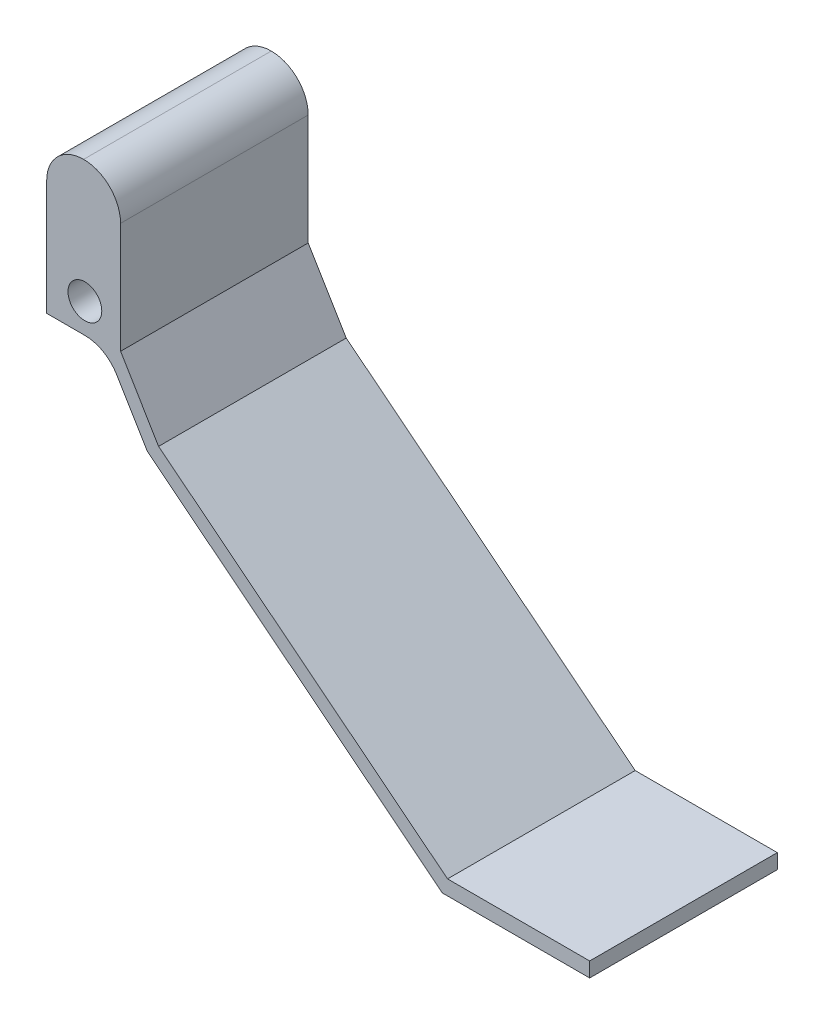
SolidWorks part; units mm, degrees
ref_plane "Front Plane" through (0, 0, 0) normal (0, 0, 1) x (1, 0, 0)
ref_plane "Top Plane" through (0, 0, 0) normal (0, 1, 0) x (1, 0, 0)
ref_plane "Right Plane" through (0, 0, 0) normal (1, 0, 0) x (0, 0, -1)
sketch "Sketch1" plane through (0, 0, 0) normal (0, 0, 1) x (1, 0, 0)
  line L0 (0, 0) -> (5.1477, -8.5733)
  line L1 (-2, -0.5543) -> (-10, -0.5543)
  line L2 (5.1477, -8.5733) -> (44.2613, -39.7201)
  line L3 (0, 0) -> (0, 20)
  line L4 (-2, -0.5543) -> (3.6191, -9.9127)
  line L5 (44.2613, -39.7201) -> (63.5, -39.7201)
  line L6 (3.6191, -9.9127) -> (43.5623, -41.7201)
  line L7 (43.5623, -41.7201) -> (63.5, -41.7201)
  line L8 (-2, -0.5543) -> (-2, 20) construction
  line L9 (0, 20) -> (-10, 20)
  line L10 (-10, 20) -> (-10, -0.5543)
  line L11 (63.5, -39.7201) -> (63.5, -41.7201)
  dimension "D1" = 10
  dimension "D2" = 2
  dimension "D3" = 50
  dimension "D4" = 20
  dimension "D5" = 8
extrude "Boss-Extrude1" add sketch "Sketch1" along normal blind 25.4 contours L10 L1 L4 L6 L7 L11 L5 L2 L0 L3 L9
fillet "Fillet1" radius 5 1 edges at (-2, -0.5543, 12.7)
sketch "Sketch2" plane through (0, 0, 25.4) normal (0, 0, 1) x (1, 0, 0)
  line L0 (-4.8299, -0.5543) -> (-4.8299, 3.4457)
  circle A0 centre (-4.8299, 3.4457) radius 2.286
  dimension "D2" = 4.572
  dimension "D1" = 4
fillet "Fillet2" radius 5 1 edges at (0, 20, 12.7)
fillet "Fillet3" radius 5 1 edges at (-10, 20, 12.7)
ref_plane "Plane1" through (0, 0, 12.7) normal (0, 0, -1) x (-1, 0, 0)
extrude "Cut-Extrude1" cut sketch "Sketch2" against normal through all contours A0
